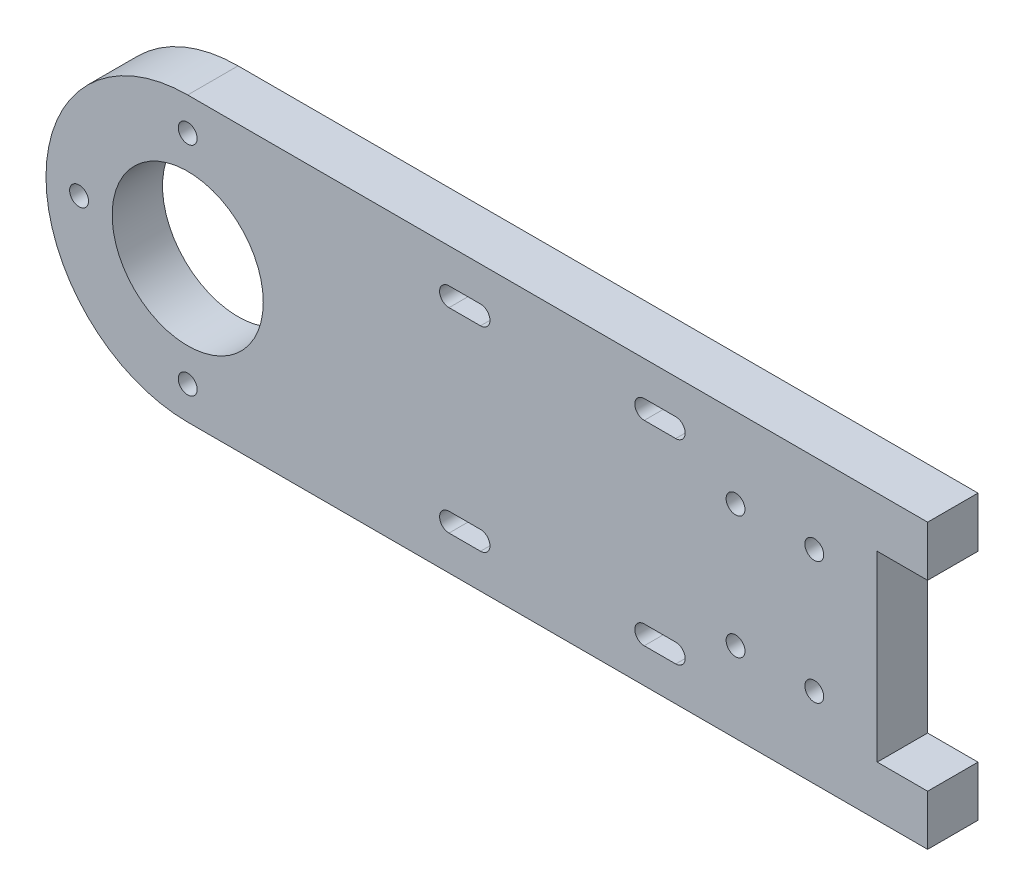
SolidWorks part; units mm, degrees
material "Pine"
ref_plane "Front Plane" through (0, 0, 0) normal (0, 0, 1) x (1, 0, 0)
ref_plane "Top Plane" through (0, 0, 0) normal (0, 1, 0) x (1, 0, 0)
ref_plane "Right Plane" through (0, 0, 0) normal (1, 0, 0) x (0, 0, -1)
sketch "Sketch1" plane through (0, 0, 0) normal (0, 0, 1) x (1, 0, 0)
  line L0 (0, 22.5) -> (0, 27.5)
  line L1 (0, 0) -> (-140, 0)
  line L2 (0, 0) -> (0, 45)
  line L3 (0, 45) -> (-140, 45)
  line L4 (-140, 0) -> (-140, 45)
  line L5 (0, 45) -> (-8, 45)
  line L6 (0, 45) -> (0, 37)
  line L7 (0, 37) -> (-8, 37)
  line L8 (-8, 45) -> (-8, 37)
  line L9 (0, 0) -> (-8, 0)
  line L10 (0, 0) -> (0, 8)
  line L11 (0, 8) -> (-8, 8)
  line L12 (-8, 0) -> (-8, 8)
  line L13 (0, 27.5) -> (-8, 27.5)
  line L14 (-8, 27.5) -> (-8, 17.5)
  line L15 (-8, 17.5) -> (0, 17.5)
  line L16 (0, 17.5) -> (0, 22.5)
  line L17 (-140, 22.5) -> (-105, 22.5)
  line L18 (-105, 22.5) -> (-110, 22.5)
  line L19 (-110, 22.5) -> (-10, 22.5)
  line L21 (-8, 8) -> (-8, 17.5)
  line L30 (-75, 18.5) -> (-85, 18.5)
  line L31 (-75, 18.5) -> (-75, 26.5)
  line L32 (-8, 17.5) -> (-8, 37)
  line L33 (-75, 26.5) -> (-85, 26.5)
  line L34 (-85, 18.5) -> (-85, 26.5)
  line L35 (-75, 18.5) -> (-85, 26.5) construction
  line L36 (-75, 26.5) -> (-85, 18.5) construction
  dimension "D1" = 140
  dimension "D2" = 45
  dimension "D3" = 5
  dimension "D4" = 10
  dimension "D5" = 8
  dimension "D6" = 8
  dimension "D7" = 8
extrude "Boss-Extrude1" add sketch "Sketch1" along normal blind 8 contours L12 L1 L2 L11 | L3 L8 L7 L2 | L31 L4 L1 L12 L21 L14 L32 L8 L3 | L34 L19 L31 L33 | L34 L30 L31 L19 region at (-4, 41, 0) region at (-80, 24.5, 0) region at (-80, 20.5, 0) region at (-9.3946, 22.5, 0) region at (-4, 4, 0)
sketch "Sketch5" plane through (0, 0, 8) normal (0, 0, 1) x (1, 0, 0)
  line L0 (-140, 22.5) -> (-117.5, 22.5)
  line L1 (-140, 0) -> (-140, 45) construction
  circle A0 centre (-117.5, 22.5) radius 12
  dimension "D2" = 24
  dimension "D1" = 22.5
extrude "Cut-Extrude4" cut sketch "Sketch5" against normal blind 8 contours A0
fillet "Fillet6" radius 22.5 2 edges at (-140, 45, 4) (-140, 0, 4)
sketch "Sketch6" plane through (0, 0, 8) normal (0, 0, 1) x (1, 0, 0)
  line L0 (0, 0) -> (-117.5, 0) construction
  line L1 (0, 45) -> (-117.5, 45) construction
  line L2 (-8, 8) -> (-8, 37) construction
  circle A0 centre (-18, 12.75) radius 1.5
  circle A1 centre (-18, 32.25) radius 1.5
  circle A2 centre (-30.5, 32.25) radius 1.5
  circle A3 centre (-30.5, 12.75) radius 1.5
  circle A4 centre (-18, 12.75) radius 1.5
  dimension "D1" = 3
  dimension "D2" = 12.75
  dimension "D3" = 12.75
  dimension "D4" = 10
  dimension "D5" = 10
extrude "Cut-Extrude5" cut sketch "Sketch6" against normal blind 8 contours A3 | A2 | A1 | A0
sketch "Sketch7" plane through (0, 0, 8) normal (0, 0, 1) x (1, 0, 0)
  line L0 (-8, 22.5) -> (-58, 22.5)
  line L1 (-8, 8) -> (-8, 37) construction
  line L2 (-58, 22.5) -> (-76, 22.5)
  line L3 (-76, 22.5) -> (-76, 38)
  line L4 (-76, 38) -> (-71, 38) construction
  line L5 (-45, 38) -> (-40, 38) construction
  line L6 (-76, 39.5) -> (-71, 39.5)
  line L7 (-76, 36.5) -> (-71, 36.5)
  line L8 (-45, 39.5) -> (-40, 39.5)
  line L9 (-45, 36.5) -> (-40, 36.5)
  line L10 (-45, 7) -> (-40, 7) construction
  line L11 (-45, 8.5) -> (-40, 8.5)
  line L12 (-45, 5.5) -> (-40, 5.5)
  line L13 (-76, 7) -> (-71, 7) construction
  line L14 (-76, 8.5) -> (-71, 8.5)
  line L15 (-76, 5.5) -> (-71, 5.5)
  arc A0 (-76, 39.5) -> (-76, 36.5) centre (-76, 38) ccw
  arc A1 (-71, 36.5) -> (-71, 39.5) centre (-71, 38) ccw
  arc A2 (-45, 39.5) -> (-45, 36.5) centre (-45, 38) ccw
  arc A3 (-40, 36.5) -> (-40, 39.5) centre (-40, 38) ccw
  arc A4 (-45, 8.5) -> (-45, 5.5) centre (-45, 7) ccw
  arc A5 (-40, 5.5) -> (-40, 8.5) centre (-40, 7) ccw
  arc A6 (-76, 8.5) -> (-76, 5.5) centre (-76, 7) ccw
  arc A7 (-71, 5.5) -> (-71, 8.5) centre (-71, 7) ccw
  point P9 (-73.5, 38)
  point P17 (-42.5, 38)
  point P24 (-42.5, 7)
  point P31 (-73.5, 7)
  dimension "D6" = 1.5
  dimension "D1" = 2
  dimension "D3" = 50
  dimension "D4" = 15.5
  dimension "D5" = 15.5
  dimension "D7" = 2.5
  dimension "D2" = 2
extrude "Cut-Extrude6" cut sketch "Sketch7" against normal blind 10 contours L7 A1 L6 A0 | L15 A7 L14 A6 | L8 A3 L9 A2 | L11 A5 L12 A4 region at (-73.5, 38, 8) region at (-73.5, 7, 8)
sketch "Sketch11" plane through (0, 0, 8) normal (0, 0, 1) x (1, 0, 0)
  circle A0 centre (-117.5, 22.5) radius 17.25
  arc A1 (-117.5, 45) -> (-140, 22.5) centre (-117.5, 22.5) ccw construction
  circle A3 centre (-134.75, 22.5) radius 1.5
  circle A4 centre (-117.5, 5.25) radius 1.5
  circle A5 centre (-117.5, 39.75) radius 1.5
  dimension "D1" = 5.25
  dimension "D2" = 3
extrude "Cut-Extrude7" cut sketch "Sketch11" against normal blind 8 contours A4 | A3 | A5
